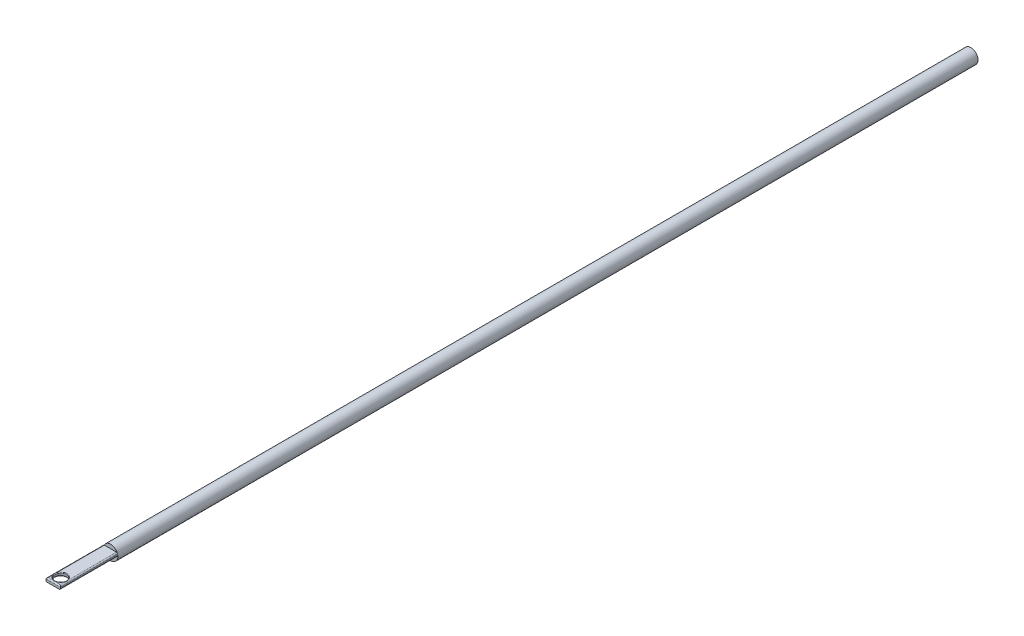
SolidWorks part; units mm, degrees
ref_plane "Ön Düzlem" through (0, 0, 0) normal (0, 0, 1) x (1, 0, 0)
ref_plane "Üst Düzlem" through (0, 0, 0) normal (0, 1, 0) x (1, 0, 0)
ref_plane "Sağ Düzlem" through (0, 0, 0) normal (1, 0, 0) x (0, 0, -1)
sketch "Sketch1" plane through (0, 0, 0) normal (0, 0, 1) x (1, 0, 0)
  circle A0 centre (0, 0) radius 6.25
  dimension "D1" = 12.5
extrude "Boss-Extrude1" add sketch "Sketch1" along normal blind 750
sketch "Sketch9" plane through (0, 0, 0) normal (0, 1, 0) x (1, 0, 0)
  line L1 (-6.1863, -750.1979) -> (6.3137, -750.1979)
  line L2 (-6.1863, -750.1979) -> (-6.1863, -800.1979)
  line L3 (-6.1863, -800.1979) -> (6.3137, -800.1979)
  line L4 (6.3137, -750.1979) -> (6.3137, -800.1979)
  line L5 (-6.1863, -750.1979) -> (6.3137, -800.1979) construction
  line L6 (-6.1863, -800.1979) -> (6.3137, -750.1979) construction
  circle A0 centre (-0.0889, -793.4973) radius 5
  point P4 (0.0637, -775.1979)
  point P5 (0, 0)
  dimension "D3" = 10
  dimension "D1" = 50
  dimension "D2" = 12.5
extrude "Boss-Extrude5" add sketch "Sketch9" along normal blind 3 separate body contours A0 | L2 L1 L4 L3 region at (-0.0889, 0, 793.4973)
fillet "Fillet3" radius 1 6 edges at (-0.0889, 0, 798.4973) (0.0637, 3, 800.1979) (6.3137, 0, 775.1979) (-6.1863, 0, 775.1979) (6.3137, 3, 775.1979) (-6.1863, 3, 775.1979)
fillet "Fillet5" radius 0.5 1 edges at (-0.0889, 3, 798.4973)
